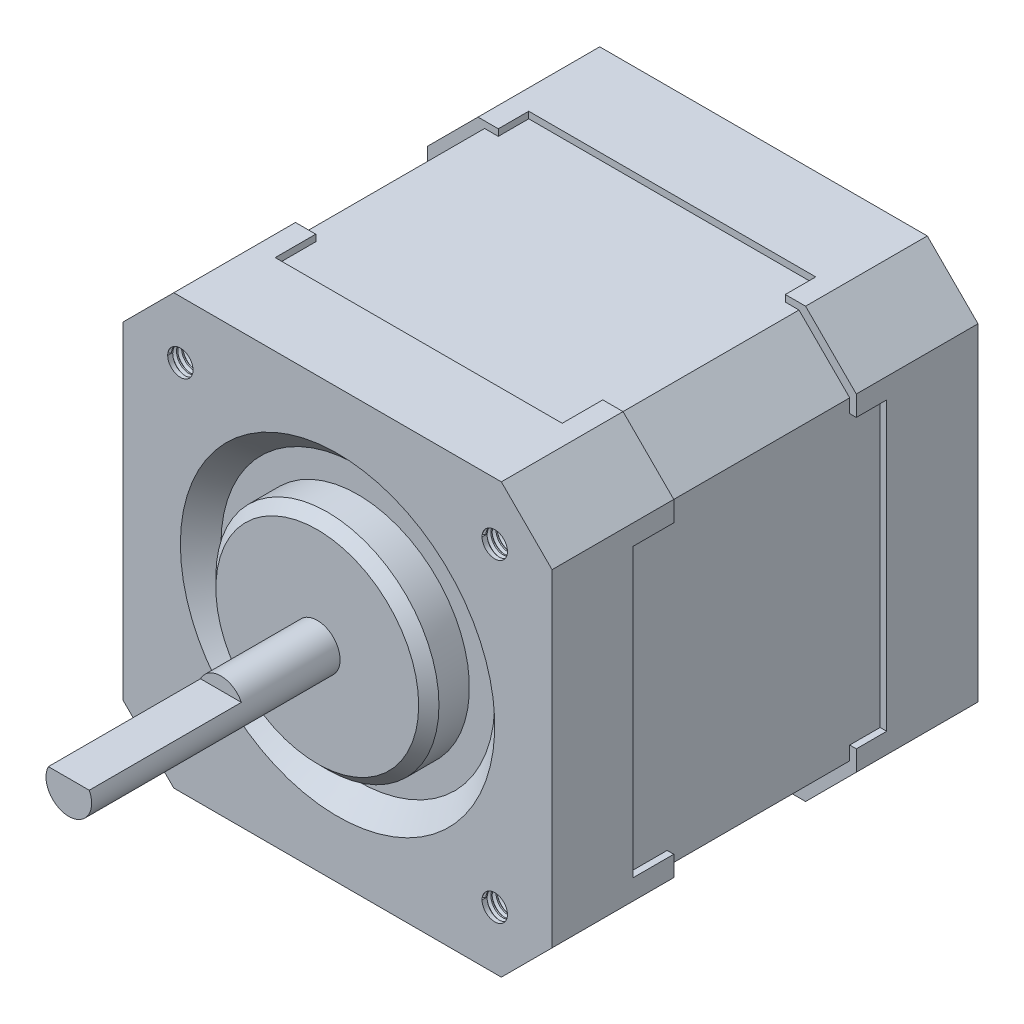
SolidWorks part; units mm, degrees
ref_plane "Front Plane" through (0, 0, 0) normal (0, 0, 1) x (1, 0, 0)
ref_plane "Top Plane" through (0, 0, 0) normal (0, 1, 0) x (1, 0, 0)
ref_plane "Right Plane" through (0, 0, 0) normal (1, 0, 0) x (0, 0, -1)
sketch "Sketch1" plane through (0, 0, 0) normal (0, 0, 1) x (1, 0, 0)
  line L0 (0, 0) -> (0, 50000) construction
  line L1 (-16.15, 21.15) -> (16.15, 21.15)
  line L2 (-21.15, 16.15) -> (-21.15, -16.15)
  line L3 (-16.15, -21.15) -> (16.15, -21.15)
  line L4 (21.15, 16.15) -> (21.15, -16.15)
  line L5 (-21.15, 21.15) -> (21.15, -21.15) construction
  line L6 (-21.15, -21.15) -> (21.15, 21.15) construction
  line L7 (0, 0) -> (50000, 0) construction
  line L8 (-21.15, 16.15) -> (-16.15, 21.15)
  line L9 (16.15, 21.15) -> (21.15, 16.15)
  line L10 (16.15, -21.15) -> (21.15, -16.15)
  line L11 (-21.15, -16.15) -> (-16.15, -21.15)
  point P0 (0, 0)
  dimension "D1" = 42.3
  dimension "D2" = 42.3
extrude "Boss-Extrude1" add sketch "Sketch1" against normal blind 12
sketch "Sketch2" plane through (0, 0, -12) normal (0, 0, -1) x (-1, 0, 0)
  line L0 (-20.5, 15.5) -> (-15.5, 20.5)
  line L1 (-15.5, -20.5) -> (15.5, -20.5)
  line L2 (-20.5, -15.5) -> (-20.5, 15.5)
  line L3 (-15.5, 20.5) -> (15.5, 20.5)
  line L4 (20.5, -15.5) -> (20.5, 15.5)
  line L5 (-20.5, -20.5) -> (20.5, 20.5) construction
  line L6 (-20.5, 20.5) -> (20.5, -20.5) construction
  line L7 (15.5, 20.5) -> (20.5, 15.5)
  line L8 (15.5, -20.5) -> (20.5, -15.5)
  line L9 (-20.5, -15.5) -> (-15.5, -20.5)
  point P0 (0, 0)
  dimension "D1" = 41
  dimension "D2" = 41
extrude "Cut-Extrude1" cut sketch "Sketch2" against normal blind 6
sketch "Sketch3" plane through (21.15, 0, 0) normal (1, 0, 0) x (0, 0, -1)
  line L0 (12, -16.15) -> (12, 16.15) construction
  line L1 (12, 14.15) -> (8, 14.15)
  line L2 (12, 14.15) -> (12, -14.15)
  line L3 (12, -14.15) -> (8, -14.15)
  line L4 (8, 14.15) -> (8, -14.15)
  line L5 (12, 16.15) -> (0, 16.15) construction
  line L6 (12, -16.15) -> (0, -16.15) construction
  dimension "D1" = 4
  dimension "D2" = 2
  dimension "D3" = 2
extrude "Cut-Extrude2" cut sketch "Sketch3" against normal up to surface (42.3 mm away) up to face at (-21.15, 0, -6)
sketch "Sketch4" plane through (0, 21.15, 0) normal (0, 1, 0) x (1, 0, 0)
  line L0 (16.15, 12) -> (-16.15, 12) construction
  line L1 (14.15, 12) -> (-14.15, 12)
  line L2 (14.15, 12) -> (14.15, 8)
  line L3 (14.15, 8) -> (-14.15, 8)
  line L4 (-14.15, 12) -> (-14.15, 8)
  line L5 (16.15, 12) -> (16.15, 0) construction
  line L6 (-16.15, 12) -> (-16.15, 0) construction
  dimension "D1" = 2
  dimension "D2" = 2
  dimension "D3" = 4
extrude "Cut-Extrude3" cut sketch "Sketch4" against normal through all both and the other way through all
sketch "Sketch5" plane through (0, 0, -6) normal (0, 0, -1) x (-1, 0, 0)
  line L0 (-15.5, -20.5) -> (-20.5, -15.5)
  line L1 (15.5, -20.5) -> (-15.5, -20.5)
  line L2 (20.5, -15.5) -> (20.5, 15.5)
  line L3 (15.5, 20.5) -> (-15.5, 20.5)
  line L4 (-20.5, -15.5) -> (-20.5, 15.5)
  line L5 (20.5, -20.5) -> (-20.5, 20.5) construction
  line L6 (20.5, 20.5) -> (-20.5, -20.5) construction
  line L7 (-15.5, 20.5) -> (-20.5, 15.5)
  line L8 (20.5, 15.5) -> (15.5, 20.5)
  line L9 (20.5, -15.5) -> (15.5, -20.5)
  point P0 (0, 0)
  dimension "D1" = 41
  dimension "D2" = 41
extrude "Boss-Extrude2" add sketch "Sketch5" along normal blind 36
ref_plane "Plane3" through (0, 0, -36) normal (0, 0, 1) x (1, 0, 0)
sketch "Sketch10" plane through (0, 0, -36) normal (0, 0, 1) x (1, 0, 0)
  line L0 (21.15, 16.15) -> (16.15, 21.15)
  line L1 (16.15, 21.15) -> (-16.15, 21.15)
  line L2 (21.15, 16.15) -> (21.15, -16.15)
  line L3 (16.15, -21.15) -> (-16.15, -21.15)
  line L4 (-21.15, 16.15) -> (-21.15, -16.15)
  line L5 (21.15, 21.15) -> (-21.15, -21.15) construction
  line L6 (21.15, -21.15) -> (-21.15, 21.15) construction
  line L7 (-16.15, 21.15) -> (-21.15, 16.15)
  line L8 (-16.15, -21.15) -> (-21.15, -16.15)
  line L9 (21.15, -16.15) -> (16.15, -21.15)
  point P0 (0, 0)
  dimension "D1" = 42.3
  dimension "D2" = 42.3
extrude "Boss-Extrude5" add sketch "Sketch10" along normal mid plane 12 separate body
sketch "Sketch11" plane through (0, 0, -30) normal (0, 0, 1) x (1, 0, 0)
  line L0 (-20.5, 15.5) -> (-15.5, 20.5)
  line L1 (-15.5, -20.5) -> (15.5, -20.5)
  line L2 (-20.5, -15.5) -> (-20.5, 15.5)
  line L3 (-15.5, 20.5) -> (15.5, 20.5)
  line L4 (20.5, -15.5) -> (20.5, 15.5)
  line L5 (-20.5, -20.5) -> (20.5, 20.5) construction
  line L6 (-20.5, 20.5) -> (20.5, -20.5) construction
  line L7 (15.5, 20.5) -> (20.5, 15.5)
  line L8 (15.5, -20.5) -> (20.5, -15.5)
  line L9 (-20.5, -15.5) -> (-15.5, -20.5)
  point P0 (0, 0)
  dimension "D1" = 41
  dimension "D2" = 41
extrude "Cut-Extrude6" cut sketch "Sketch11" against normal blind 6
sketch "Sketch12" plane through (21.15, 0, 0) normal (1, 0, 0) x (0, 0, -1)
  line L0 (30, -16.15) -> (30, 16.15) construction
  line L1 (30, 14.15) -> (33, 14.15)
  line L2 (30, 14.15) -> (30, -14.15)
  line L3 (30, -14.15) -> (33, -14.15)
  line L4 (33, 14.15) -> (33, -14.15)
  line L5 (30, 16.15) -> (42, 16.15) construction
  line L6 (30, -16.15) -> (42, -16.15) construction
  dimension "D1" = 2
  dimension "D2" = 2
  dimension "D3" = 3
extrude "Cut-Extrude7" cut sketch "Sketch12" against normal through all
sketch "Sketch13" plane through (0, 0, 0) normal (1, 0, 0) x (0, 0, -1)
  line L0 (0, 0) -> (50000, 0) construction
  line L1 (0, 0) -> (0, 50000) construction
  line L2 (0, 0) -> (0, 15.5)
  line L3 (0, 15.5) -> (2, 13.5)
  line L4 (2, 13.5) -> (2, 0)
  line L5 (2, 0) -> (0, 0)
  dimension "D1" = 15.5
  dimension "D2" = 135
  dimension "D3" = 2
revolve "Cut-Revolve1" cut sketch "Sketch13" angle 360 about L5
sketch "Sketch14" plane through (0, 0, -2) normal (0, 0, 1) x (1, 0, 0)
  circle A0 centre (0, 0) radius 11
  dimension "D1" = 22
extrude "Boss-Extrude6" add sketch "Sketch14" along normal blind 4
chamfer "Chamfer1" distance 1 angle 45 1 edges at (11, 0, 2)
sketch "Sketch15" plane through (0, 0, 2) normal (0, 0, 1) x (1, 0, 0)
  circle A0 centre (0, 0) radius 2.25
  dimension "D1" = 4.5
extrude "Boss-Extrude7" add sketch "Sketch15" along normal blind 24.5
sketch "Sketch16" plane through (0, 0, 26.5) normal (0, 0, 1) x (1, 0, 0)
  line L0 (-2.0156, 1) -> (2.0156, 1)
  circle A0 centre (0, 0) radius 2.25 construction
  arc A1 (2.0156, 1) -> (-2.0156, 1) centre (0, 0) ccw
  dimension "D1" = 1
extrude "Cut-Extrude8" cut sketch "Sketch16" against normal blind 15
sketch "Sketch17" plane through (0, 21.15, 0) normal (0, 1, 0) x (1, 0, 0)
  line L0 (16.15, 30) -> (-16.15, 30) construction
  line L1 (-14.15, 30) -> (14.15, 30)
  line L2 (-14.15, 30) -> (-14.15, 33)
  line L3 (-14.15, 33) -> (14.15, 33)
  line L4 (14.15, 30) -> (14.15, 33)
  line L5 (-16.15, 30) -> (-16.15, 42) construction
  line L6 (16.15, 30) -> (16.15, 42) construction
  point P6 (-14.15, 31.5)
  dimension "D1" = 2
  dimension "D2" = 2
  dimension "D3" = 3
extrude "Cut-Extrude9" cut sketch "Sketch17" against normal through all
hole_wizard "M3 Tapped Hole1" positions "Sketch18" profile "Sketch20" tap size "M3" standard "ISO"
sketch "Sketch18" plane through (0, 0, 0) normal (0, 0, 1) x (1, 0, 0)
  line L1 (-15.5, 15.5) -> (15.5, 15.5) construction
  line L2 (-15.5, 15.5) -> (-15.5, -15.5) construction
  line L3 (-15.5, -15.5) -> (15.5, -15.5) construction
  line L4 (15.5, 15.5) -> (15.5, -15.5) construction
  line L5 (-15.5, 15.5) -> (15.5, -15.5) construction
  line L6 (-15.5, -15.5) -> (15.5, 15.5) construction
  point P0 (-15.5, 15.5)
  point P2 (15.5, 15.5)
  point P4 (-15.5, -15.5)
  point P6 (15.5, -15.5)
  point P10 (0, 0)
  dimension "D7" = 31
sketch "Sketch20" plane through (-15.5, 15.5, 0) normal (1, 0, 0) x (0, -1, 0)
  line L0 (0, 0) -> (0, 5.2511)
  line L1 (0, 5.2511) -> (1.25, 4.5)
  line L2 (1.25, 4.5) -> (1.25, 0)
  line L5 (1.25, 0) -> (0, 0)
  line L10 (0, 5.2511) -> (-1.25, 4.5) construction
  line L11 (0, -6.35) -> (0, 107.95) construction
  dimension "Tap Drill Dia." = 2.5
  dimension "Tap Drill Depth" = 4.5
  dimension "Drill Angle" = 118
thread "Thread1" pitch 0.5 start angle 0, offset 0, length 0, pitch 0.5, diameter 2.5
ref_plane "Plane4" through (-16.75, 15.5, 0) normal (0, -1, 0) x (-1, 0, 0)
sketch "Thread Profile1" plane through (-16.75, 15.5, 0) normal (0, -1, 0) x (-1, 0, 0)
  line L0 (0, 0) -> (0, 0.5) construction
  line L1 (0, 0) -> (0.2706, 0.1562)
  line L2 (0.2706, 0.1562) -> (0.2706, 0.2187)
  line L3 (0.2706, 0.2187) -> (0, 0.375)
  line L4 (0.2706, 0.1875) -> (0, 0.1875) construction
  line L11 (0, 0) -> (0, 0.375)
  point P2 (0, 0)
  dimension "Pitch" = 0.5
  dimension "Profile_Angle" = 60
  dimension "Profile_Land" = 0.0625
  dimension "Profile_Height" = 0.2706
thread "Thread2" pitch 0.5 profile "Thread Profile2" start angle 0, offset 0, length 0, pitch 0.5, diameter 2.5
ref_plane "Plane5" through (14.25, 15.5, 0) normal (0, -1, 0) x (-1, 0, 0)
sketch "Thread Profile2" plane through (14.25, 15.5, 0) normal (0, -1, 0) x (-1, 0, 0)
  line L0 (0, 0) -> (0, 0.5) construction
  line L1 (0, 0) -> (0.2706, 0.1562)
  line L2 (0.2706, 0.1562) -> (0.2706, 0.2187)
  line L3 (0.2706, 0.2187) -> (0, 0.375)
  line L4 (0.2706, 0.1875) -> (0, 0.1875) construction
  line L11 (0, 0) -> (0, 0.375)
  point P2 (0, 0)
  dimension "Pitch" = 0.5
  dimension "Profile_Angle" = 60
  dimension "Profile_Land" = 0.0625
  dimension "Profile_Height" = 0.2706
thread "Thread3" pitch 0.5 profile "Thread Profile3" start angle 0, offset 0, length 0, pitch 0.5, diameter 2.5
ref_plane "Plane6" through (-16.75, -15.5, 0) normal (0, -1, 0) x (-1, 0, 0)
sketch "Thread Profile3" plane through (-16.75, -15.5, 0) normal (0, -1, 0) x (-1, 0, 0)
  line L0 (0, 0) -> (0, 0.5) construction
  line L1 (0, 0) -> (0.2706, 0.1562)
  line L2 (0.2706, 0.1562) -> (0.2706, 0.2187)
  line L3 (0.2706, 0.2187) -> (0, 0.375)
  line L4 (0.2706, 0.1875) -> (0, 0.1875) construction
  line L11 (0, 0) -> (0, 0.375)
  point P2 (0, 0)
  dimension "Pitch" = 0.5
  dimension "Profile_Angle" = 60
  dimension "Profile_Land" = 0.0625
  dimension "Profile_Height" = 0.2706
thread "Thread4" pitch 0.5 profile "Thread Profile4" start angle 0, offset 0, length 0, pitch 0.5, diameter 2.5
ref_plane "Plane7" through (14.25, -15.5, 0) normal (0, -1, 0) x (-1, 0, 0)
sketch "Thread Profile4" plane through (14.25, -15.5, 0) normal (0, -1, 0) x (-1, 0, 0)
  line L0 (0, 0) -> (0, 0.5) construction
  line L1 (0, 0) -> (0.2706, 0.1562)
  line L2 (0.2706, 0.1562) -> (0.2706, 0.2187)
  line L3 (0.2706, 0.2187) -> (0, 0.375)
  line L4 (0.2706, 0.1875) -> (0, 0.1875) construction
  line L11 (0, 0) -> (0, 0.375)
  point P2 (0, 0)
  dimension "Pitch" = 0.5
  dimension "Profile_Angle" = 60
  dimension "Profile_Land" = 0.0625
  dimension "Profile_Height" = 0.2706
equation "\"D1@Sketch13\"=31/2"
equation "\"D2@Sketch13\"=180-45"
